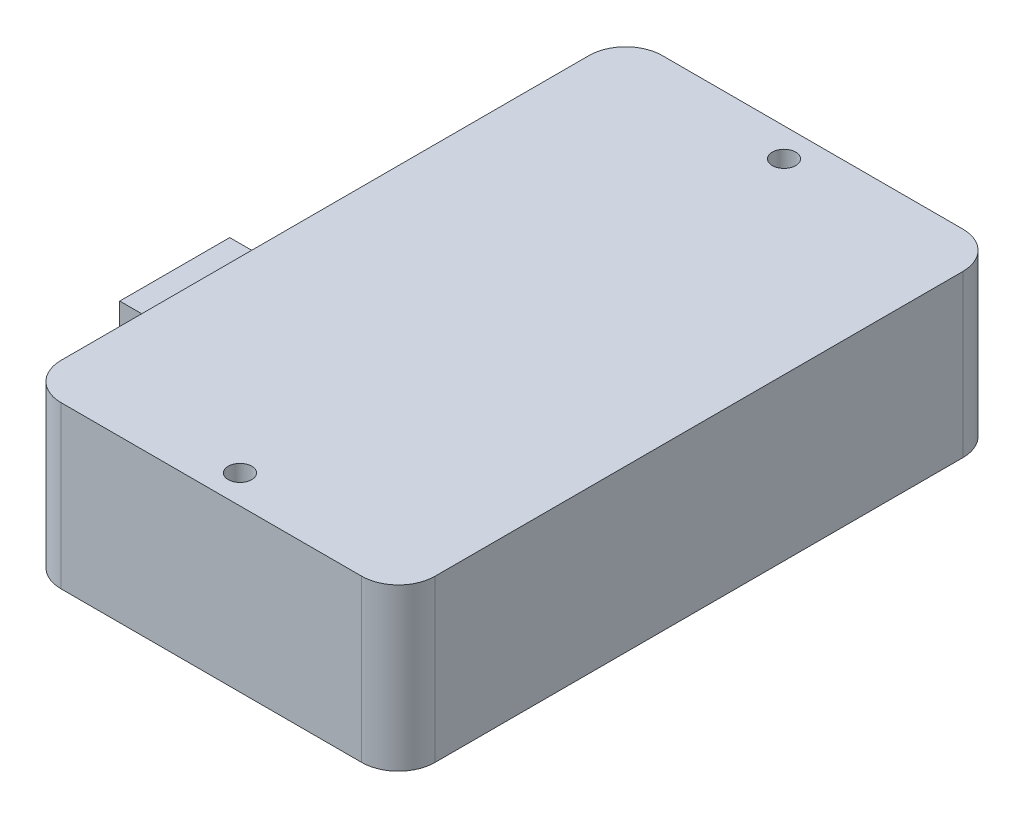
SolidWorks part; units mm, degrees
ref_plane "Front Plane" through (0, 0, 0) normal (0, 0, 1) x (1, 0, 0)
ref_plane "Top Plane" through (0, 0, 0) normal (0, 1, 0) x (1, 0, 0)
ref_plane "Right Plane" through (0, 0, 0) normal (1, 0, 0) x (0, 0, -1)
sketch "Sketch1" plane through (0, 0, 0) normal (0, 1, 0) x (1, 0, 0)
  line L0 (-25.5, 0) -> (25.5, 0) construction
  line L1 (-25.5, -41) -> (25.5, -41)
  line L2 (-25.5, -41) -> (-25.5, 41)
  line L3 (-25.5, 41) -> (25.5, 41)
  line L4 (25.5, -41) -> (25.5, 41)
  line L5 (-25.5, -41) -> (25.5, 41) construction
  line L6 (-25.5, 41) -> (25.5, -41) construction
  line L7 (11.5, -41) -> (11.5, -56) construction
  line L9 (25.5, -25.5) -> (25.5, -17)
  line L14 (-25.5, -3) -> (-35.5, -3)
  line L15 (-25.5, -3) -> (-25.5, -18)
  line L16 (-25.5, -18) -> (-35.5, -18)
  line L17 (-35.5, -3) -> (-35.5, -18)
  circle A0 centre (0, -37.1) radius 1.6
  circle A1 centre (0, 37.1) radius 1.6
  point P0 (0, 0)
  dimension "D3" = 3.2
  dimension "D1" = 51
  dimension "D2" = 82
  dimension "D4" = 3.9
  dimension "D8" = 15
  dimension "D9" = 38
  dimension "D10" = 10
  dimension "D11" = 14
  dimension "D12" = 15
extrude "Boss-Extrude1" add sketch "Sketch1" along normal blind 22 contours L1 L4 L3 L2 A0 A1 region at (0, 0, 0)
extrude "Boss-Extrude2" add sketch "Sketch1<3>" along normal blind 15 contours L4 | L14 L17 L16 L2 region at (-30.5, 0, 10.5)
sketch "Sketch1<3>" plane through (0, 0, 0) normal (0, 1, 0) x (1, 0, 0) same geometry as "Sketch1"
fillet "Fillet1" radius 5 4 edges at (-25.5, 11, -41) (25.5, 11, -41) (25.5, 11, 41) (-25.5, 11, 41)
equation "\"D4@Sketch1\"=2.2+1.7"
